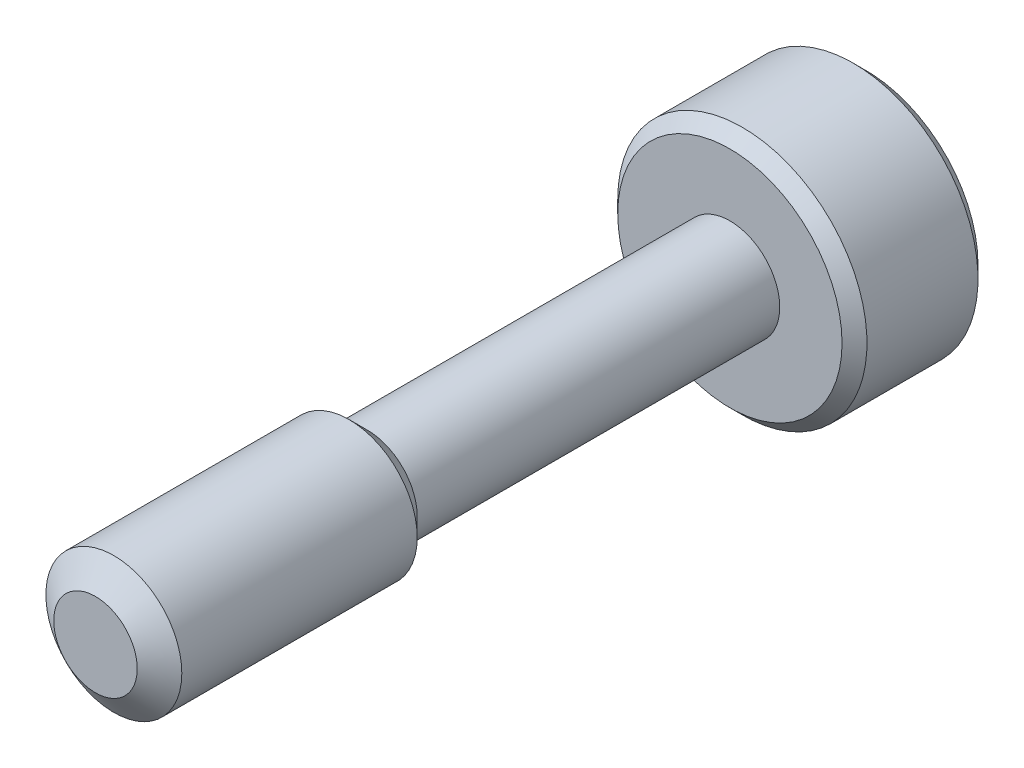
SolidWorks part; units mm, degrees
other "DetailItem1"
material "AISI 304"
ref_plane "Front Plane" through (0, 0, 0) normal (0, 0, 1) x (1, 0, 0)
ref_plane "Top Plane" through (0, 0, 0) normal (0, 1, 0) x (1, 0, 0)
ref_plane "Right Plane" through (0, 0, 0) normal (1, 0, 0) x (0, 0, -1)
sketch "Sketch1" plane through (0, 0, 0) normal (0, 0, 1) x (1, 0, 0)
  circle A0 centre (0, 0) radius 1.5
  dimension "OD" = 3
extrude "Extrude1" add sketch "Sketch1" against normal blind 14
sketch "Sketch2" plane through (0, 0, 0) normal (0, 0, 1) x (1, 0, 0)
  circle A0 centre (0, 0) radius 1.5 construction
  circle A1 centre (0, 0) radius 1.5
curve "Helix/Spiral1" pitch 0.5 height 14.5 turns 29 parameters "pitch"=0.5
sketch "Sketch3" plane through (0, 0, 0) normal (1, 0, 0) x (0, 0, -1)
  line L0 (-0.4375, 1.5) -> (-0.25, 1.1752)
  line L1 (-0.25, 1.1752) -> (-0.1875, 1.1752)
  line L2 (-0.1875, 1.1752) -> (0, 1.5)
  line L3 (-0.4375, 1.5) -> (0, 1.5)
  line L4 (-0.2188, 1.5) -> (-0.2188, 1.1752) construction
  line L5 (-0.3438, 1.3376) -> (-0.0938, 1.3376) construction
  line L6 (0, 1.5) -> (0, -1.5) construction
  dimension "D1" = 0.0625
  dimension "D2" = 0.25
  dimension "D3" = 60
sweep "Cut-Sweep1" [suppressed] cut profiles "Sketch3" path "Helix/Spiral1"
sketch "Sketch6" plane through (0, 0, -14) normal (0, 0, -1) x (-1, 0, 0)
  circle A0 centre (0, 0) radius 2.75
  dimension "head dia" = 5.5
extrude "Extrude2" add sketch "Sketch6" along normal blind 3
sketch "Sketch7" plane through (0, 0, -17) normal (0, 0, -1) x (-1, 0, 0)
  line L1 (0, 1.4434) -> (-1.25, 0.7217)
  line L2 (-1.25, 0.7217) -> (-1.25, -0.7217)
  line L3 (-1.25, -0.7217) -> (0, -1.4434)
  line L4 (0, -1.4434) -> (1.25, -0.7217)
  line L5 (1.25, -0.7217) -> (1.25, 0.7217)
  line L6 (1.25, 0.7217) -> (0, 1.4434)
  circle A0 centre (0, 0) radius 1.25 construction
  dimension "hex dia" = 2.5
extrude "Cut-Extrude1" cut sketch "Sketch7" against normal blind 1.875
sketch "Sketch8" plane through (0, 0, -17) normal (0, 0, -1) x (-1, 0, 0)
  circle A0 centre (0, 0) radius 1.4434
extrude "Cut-Extrude2" cut sketch "Sketch8" against normal through all draft 45
chamfer "Chamfer1" distance 0.275 angle 45 2 edges at (-2.75, 0, -17) (-2.75, 0, -14)
sketch "Sketch10" plane through (0, 0, -14) normal (0, 0, 1) x (1, 0, 0)
  circle A1 centre (0, 0) radius 1.5
  circle A2 centre (0, 0) radius 1.5
  dimension "D1" = 0
ref_plane "Plane1" through (0, 0, 0) normal (0, 0, 1) x (1, 0, 0)
extrude "partial thread" [suppressed] add sketch "Sketch10" along normal up to surface (36 mm away) separate body
chamfer "Chamfer2" [suppressed] distance 0.06 angle 45
combine bodies "Combine1" [suppressed] operation type add bodies to combine 107 108
sketch "Sketch9" plane through (0, 0, 0) normal (1, 0, 0) x (0, 0, -1)
  line L0 (0, 1.5) -> (0, -1.5) construction
  line L1 (1.25, 1.5) -> (1.25, -1.5) construction
  dimension "D1" = 1.25
sketch "Sketch11" plane through (0, 0, -14) normal (0, 0, 1) x (1, 0, 0)
  circle A0 centre (0, 0) radius 1.1
  dimension "D1" = 2.2
extrude "Cut-Extrude3" cut sketch "Sketch11" along normal blind 8 flip side to cut
sketch "Sketch4" plane through (0, 0, 0) normal (1, 0, 0) x (0, 0, -1)
  line L0 (0.4053, 1.5) -> (0, 0.9212)
  line L1 (0, 0.9212) -> (0, 1.5)
  line L2 (0.4053, 1.5) -> (0, 1.5)
  line L3 (-0.4375, 1.5) -> (0, 1.5) construction
  line L4 (0, 0) -> (7.0209, 0) construction
  line L5 (3, 0) -> (3, -2.0566) construction
  line L6 (5.6, 1.5) -> (6, 1.5)
  line L7 (6, 1.1) -> (6, 1.5)
  line L8 (5.6, 1.5) -> (6, 1.1)
  dimension "D1" = 55
  dimension "D2" = 0.254
  dimension "D3" = 3
  dimension "D4" = 1.1
revolve "Cut-Revolve1" cut sketch "Sketch4" angle 360 about L4
equation "\"D3@Helix/Spiral1\" = \"screw length@Extrude1\"+\"pitch@Helix/Spiral1\""
equation "\"D1@Sketch3\" = \"pitch@Helix/Spiral1\"*.125"
equation "\"D2@Sketch3\" = \"pitch@Helix/Spiral1\"*.5"
equation "\"D1@Cut-Extrude1\" = \"hex dia@Sketch7\"*.75"
equation "\"D1@Chamfer1\" = \"head dia@Sketch6\"*.05"
equation "\"D1@Sketch9\" = \"pitch@Helix/Spiral1\"*2.5"
equation "\"D1@Chamfer2\"=\"OD@Sketch1\"*.02"
